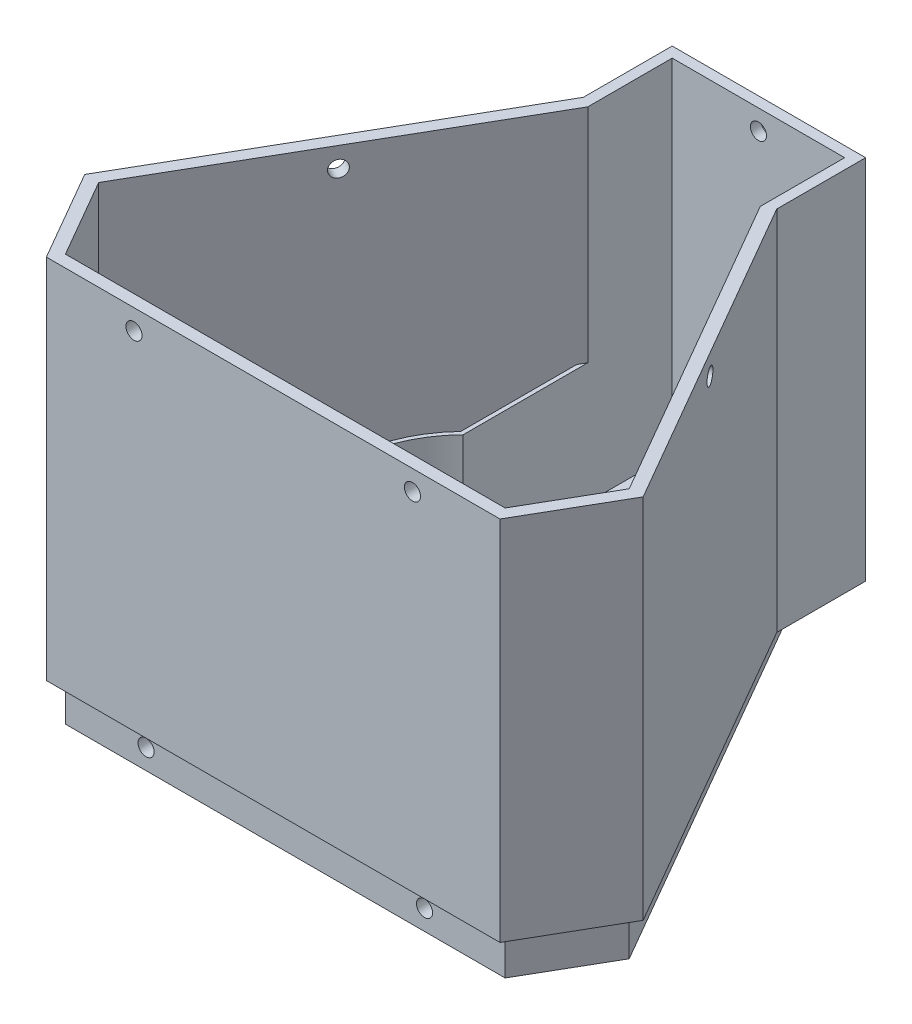
SolidWorks part; units mm, degrees
ref_plane "Front Plane" through (0, 0, 0) normal (0, 0, 1) x (1, 0, 0)
ref_plane "Top Plane" through (0, 0, 0) normal (0, 1, 0) x (1, 0, 0)
ref_plane "Right Plane" through (0, 0, 0) normal (1, 0, 0) x (0, 0, -1)
sketch "Sketch1" plane through (0, 0, 0) normal (0, 1, 0) x (1, 0, 0)
  line L0 (0, 44.1373) -> (0, -47.5886) construction
  line L1 (0, 0) -> (44.414, 25.6424) construction
  line L2 (-13, 72.4944) -> (13, 72.4944)
  line L3 (13, 72.4944) -> (21.4, 57.9452)
  line L4 (-11.2679, 69.4944) -> (11.2679, 69.4944)
  line L5 (11.2679, 69.4944) -> (38.5429, 22.2528)
  line L6 (-9.5359, 66.4944) -> (9.5359, 66.4944)
  line L7 (9.5359, 66.4944) -> (35.9449, 20.7528)
  line L8 (-24, 75.4944) -> (24, 75.4944)
  line L9 (24, 75.4944) -> (24, 53.4419)
  line L10 (-21.4, 72.8944) -> (21.4, 72.8944)
  line L11 (21.4, 72.8944) -> (21.4, 51.9452)
  line L12 (-21.4, 72.8944) -> (-21.4, 51.9452)
  line L13 (-24, 75.4944) -> (-24, 53.4419)
  line L14 (-9.5359, 66.4944) -> (-35.9449, 20.7528)
  line L15 (-11.2679, 69.4944) -> (-38.5429, 22.2528)
  line L16 (-13, 72.4944) -> (-21.4, 57.9452)
  line L17 (69.282, -24.9889) -> (41.141, 23.7528)
  line L18 (65.8179, -24.9889) -> (38.5429, 22.2528)
  line L19 (62.3538, -24.9889) -> (35.9449, 20.7528)
  line L20 (69.282, -24.9889) -> (56.282, -47.5056)
  line L21 (65.8179, -24.9889) -> (54.55, -44.5056)
  line L22 (62.3538, -24.9889) -> (52.8179, -41.5056)
  line L23 (56.282, -47.5056) -> (0, -47.5056)
  line L24 (54.55, -44.5056) -> (0, -44.5056)
  line L25 (52.8179, -41.5056) -> (0, -41.5056)
  line L26 (-56.282, -47.5056) -> (0, -47.5056)
  line L27 (-54.55, -44.5056) -> (0, -44.5056)
  line L28 (-52.8179, -41.5056) -> (0, -41.5056)
  line L29 (-56.282, -47.5056) -> (-69.282, -24.9889)
  line L30 (-54.55, -44.5056) -> (-65.8179, -24.9889)
  line L31 (-52.8179, -41.5056) -> (-62.3538, -24.9889)
  line L32 (-69.282, -24.9889) -> (-41.141, 23.7528)
  line L33 (-65.8179, -24.9889) -> (-38.5429, 22.2528)
  line L34 (-62.3538, -24.9889) -> (-35.9449, 20.7528)
  line L35 (24, 53.4419) -> (41.141, 23.7528)
  line L36 (-24, 53.4419) -> (-41.141, 23.7528)
  circle A0 centre (0, 0) radius 6
  circle A1 centre (0, 0) radius 8.6
  circle A2 centre (0, 0) radius 9.6
  point P22 (0, 72.8944)
  point P24 (0, 75.4944)
  point P26 (0, 66.4944)
  point P28 (0, 69.4944)
  point P30 (0, 72.4944)
  point P57 (0, 0)
  dimension "D12" = 12
  dimension "D13" = 17.2
  dimension "D14" = 19.2
  dimension "D1" = 3
  dimension "D2" = 42.8
  dimension "D3" = 3
  dimension "D4" = 3
  dimension "D5" = 3
  dimension "D6" = 3
  dimension "D7" = 2.6
  dimension "D8" = 26
  dimension "D10" = 120
  dimension "D11" = 2.6
  dimension "D9" = 3
extrude "Boss-Extrude1" add sketch "Sketch1" along normal blind 10 contours A1 A0 | A2 A1 | L34 L31 L28 L25 L22 L19 L7 L6 L14 A2 | L33 L30 L27 L24 L21 L18 L5 L4 L15 L31 L34 L14 L6 L7 L19 L22 L25 L28 region at (-14.8259, 0, -59.8491) region at (0, 0, -64.8447) region at (-8.3568, 0, 0) region at (-9.3285, 0, 0)
extrude "Boss-Extrude2" add sketch "Sketch1<3>" along normal blind 6 from surface contours L13 L36 L32 L29 L26 L23 L20 L17 L35 L9 L8 L30 L33 L15 L12 L10 L11 L5 L18 L21 L24 L27 | L34 L31 L28 L25 L22 L19 L7 L6 L14 | L16 L2 L3 L11 L10 L12 | L2 L16 L12 L15 L4 L5 L11 L3 | L33 L30 L27 L24 L21 L18 L5 L4 L15 L31 L34 L14 L6 L7 L19 L22 L25 L28 | A2 A1 | A1 A0 region at (-17.5926, 0, -65.4465) region at (0, 0, -72.0197) region at (-14.8259, 0, -59.8491) region at (0, 0, -64.8447) region at (0, 0, -73.6416) region at (-8.3568, 0, 0) region at (-9.3285, 0, 0) starting at face at (0, 10, 6)
sketch "Sketch1<3>" plane through (0, 0, 0) normal (0, 1, 0) x (1, 0, 0) same geometry as "Sketch1"
extrude "Boss-Extrude3" add sketch "Sketch1<4>" along normal blind 85 from surface contours L13 L36 L32 L29 L26 L23 L20 L17 L35 L9 L8 L30 L33 L15 L12 L10 L11 L5 L18 L21 L24 L27 region at (0, 0, -73.6416) starting at face at (0, 16, -14.1105)
sketch "Sketch1<4>" plane through (0, 0, 0) normal (0, 1, 0) x (1, 0, 0) same geometry as "Sketch1"
sketch "Sketch3" plane through (38.5429, 0, -22.2528) normal (0.866, 0, -0.5) x (-0.5, 0, -0.866)
  line L0 (-54.55, 5) -> (54.55, 5) construction
  line L1 (-54.55, 10) -> (-54.55, 0) construction
  line L2 (54.55, 10) -> (54.55, 0) construction
  line L3 (0, 0) -> (0, 10) construction
  line L4 (-54.55, 10) -> (54.55, 10) construction
  line L5 (36.6862, 8.7) -> (38.8224, 5)
  line L6 (-38.8224, 5) -> (-36.6862, 1.3)
  line L7 (-36.6862, 1.3) -> (-32.4138, 1.3)
  line L8 (-32.4138, 1.3) -> (-30.2776, 5)
  line L9 (-30.2776, 5) -> (-32.4138, 8.7)
  line L10 (-32.4138, 8.7) -> (-36.6862, 8.7)
  line L11 (-36.6862, 8.7) -> (-38.8224, 5)
  line L12 (32.4138, 8.7) -> (36.6862, 8.7)
  line L13 (30.2776, 5) -> (32.4138, 8.7)
  line L14 (32.4138, 1.3) -> (30.2776, 5)
  line L15 (36.6862, 1.3) -> (32.4138, 1.3)
  line L16 (38.8224, 5) -> (36.6862, 1.3)
  line L17 (-38.8224, 5) -> (-38.8224, 0)
  line L18 (-54.55, 0) -> (54.55, 0) construction
  line L19 (-38.8224, 0) -> (-30.2776, 0)
  line L20 (-30.2776, 0) -> (-30.2776, 5)
  line L21 (38.8224, 5) -> (38.8224, 0)
  line L22 (38.8224, 0) -> (30.2776, 0)
  line L23 (30.2776, 0) -> (30.2776, 5)
  circle A0 centre (-34.55, 5) radius 2
  circle A1 centre (-34.55, 5) radius 3.7 construction
  circle A2 centre (34.55, 5) radius 3.7 construction
  circle A3 centre (34.55, 5) radius 2
  circle A4 centre (-34.55, 5) radius 3
  circle A5 centre (34.55, 5) radius 3
  line M1 (-54.55, 0) -> (54.55, 0)
  dimension "D1" = 4
  dimension "D4" = 6
  dimension "D2" = 7.4
  dimension "D3" = 20
extrude "Cut-Extrude1" cut sketch "Sketch3" against normal blind 3 contours A0 | A3 region at (55.8179, 5, 7.6684) region at (21.2679, 5, -52.1739)
extrude "Cut-Extrude7" cut sketch "Sketch3<8>" against normal blind 6 from offset 3 contours L10 L11 L6 L7 L8 L9 A0 | L20 L8 L7 L6 L17 M1 | L16 L5 L12 L13 L14 L15 A3 | L23 L21 L16 L15 L14 M1 | A3 | A4 A0 | A0 | A5 A3 region at (55.8179, 0.099, 7.6684) region at (19.7147, 6.7935, -54.8642) region at (19.1813, 2.5, -55.7882) region at (54.2647, 3.2065, 4.9782) region at (55.8179, 5, 7.6684) region at (21.2679, 5, -52.1739) region at (57.2755, 5, 10.193) region at (22.7255, 5, -49.6493) offset against normal yes
sketch "Sketch3<8>" plane through (38.5429, 0, -22.2528) normal (0.866, 0, -0.5) x (-0.5, 0, -0.866) same geometry as "Sketch3"
extrude "Cut-Extrude8" cut sketch "Sketch3<11>" against normal blind 16 from offset 3 contours A4 A0 | A5 A3 | A0 | A3 region at (55.8179, 5, 7.6684) region at (21.2679, 5, -52.1739) region at (57.2755, 5, 10.193) region at (22.7255, 5, -49.6493) offset against normal yes
sketch "Sketch3<11>" plane through (38.5429, 0, -22.2528) normal (0.866, 0, -0.5) x (-0.5, 0, -0.866) same geometry as "Sketch3"
ref_axis "Axis1" through (0, -5.05, 0) along (0, 1, 0)
pattern_circular "CirPattern1" count 3 over 360 about axis through (0, -5.05, 0) along (0, 1, 0) of "Cut-Extrude1", "Cut-Extrude7", "Cut-Extrude8"
sketch "Sketch4" plane through (0, 0, -72.8944) normal (0, 0, 1) x (1, 0, 0)
  line L0 (0, 101) -> (0, 16) construction
  line L1 (21.4, 101) -> (-21.4, 101) construction
  line L2 (21.4, 16) -> (-21.4, 16) construction
  circle A0 centre (0, 30) radius 2
  circle A1 centre (0, 96) radius 2
  dimension "D2" = 4
  dimension "D4" = 4
  dimension "D1" = 14
  dimension "D3" = 5
extrude "Cut-Extrude9" cut sketch "Sketch4" against normal blind 16
sketch "Sketch5" plane through (0, 16, 0) normal (0, 1, 0) x (1, 0, 0)
  line L0 (21.4, 51.9452) -> (21.4, 21.0247)
  line L1 (-21.4, 21.0247) -> (-21.4, 51.9452)
  line L2 (22.4, 50.2132) -> (22.4, 21.4299)
  line L3 (65.8179, -24.9889) -> (21.4, 51.9452) construction
  line L4 (-22.4, 21.4299) -> (-22.4, 50.2132)
  line L5 (-21.4, 51.9452) -> (-65.8179, -24.9889) construction
  line L6 (-22.4, 50.2132) -> (-21.4, 51.9452)
  line L7 (22.4, 50.2132) -> (21.4, 51.9452)
  arc A0 (21.4, 21.0247) -> (-21.4, 21.0247) centre (0, 0) cw
  arc A1 (22.4, 21.4299) -> (-22.4, 21.4299) centre (0, 0) cw
  dimension "D2" = 1
  dimension "D3" = 60
  dimension "D4" = 62
  dimension "D1" = 1
extrude "Boss-Extrude4" add sketch "Sketch5" along normal blind 30
sketch "Sketch6" plane through (41.141, 0, -23.7528) normal (0.866, 0, -0.5) x (-0.5, 0, -0.866)
  line L0 (-11, 101) -> (-11, 10) construction
  line L1 (34.282, 101) -> (-56.282, 101) construction
  line L2 (34.282, 10) -> (-56.282, 10) construction
  circle A0 centre (-11, 96) radius 2
  dimension "D1" = 4
  dimension "D2" = 5
extrude "Cut-Extrude10" cut sketch "Sketch6" against normal blind 30
sketch "Sketch8" plane through (0, 0, 44.5056) normal (0, 0, -1) x (-1, 0, 0)
  line L0 (54.55, 101) -> (-54.55, 101) construction
  line L1 (-54.55, 101) -> (-54.55, 16) construction
  circle A0 centre (-34.55, 96) radius 2
  point P6 (-49.6026, 94.7564)
  point P7 (0, 0)
  point P8 (0, 0)
  dimension "D3" = 4
  dimension "D1" = 5
  dimension "D2" = 20
extrude "Cut-Extrude11" cut sketch "Sketch8" against normal blind 30
mirror "Mirror1" about plane through (0, 0, 0) normal (1, 0, 0) of "Cut-Extrude11", "Cut-Extrude10"
extrude "Cut-Extrude12" cut sketch "Sketch1<5>" against normal blind 3 from surface contours A2 A1 | A1 A0 region at (-8.3568, 0, 0) region at (-9.3285, 0, 0) starting at face at (0, 16, 6)
sketch "Sketch1<5>" plane through (0, 0, 0) normal (0, 1, 0) x (1, 0, 0) same geometry as "Sketch1"
extrude "Cut-Extrude13" cut sketch "Sketch1<6>" against normal blind 7 from surface contours A1 A0 region at (-8.3568, 0, 0) starting at face at (0, 16, 9.6)
sketch "Sketch1<6>" plane through (0, 0, 0) normal (0, 1, 0) x (1, 0, 0) same geometry as "Sketch1"
